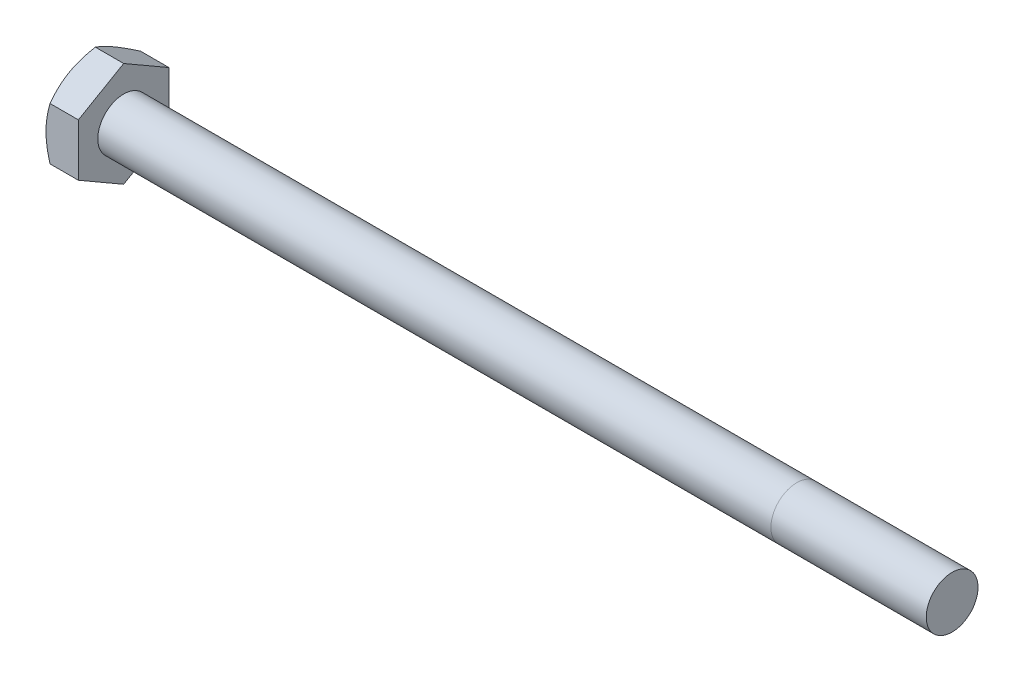
SolidWorks part; units mm, degrees
material "Alloy Steel"
ref_plane "Front Plane" through (0, 0, 0) normal (0, 0, 1) x (1, 0, 0)
ref_plane "Top Plane" through (0, 0, 0) normal (0, 1, 0) x (1, 0, 0)
ref_plane "Right Plane" through (0, 0, 0) normal (1, 0, 0) x (0, 0, -1)
sketch "Sketch1" plane through (0, 0, 0) normal (0, 0, 1) x (1, 0, 0)
  line L0 (-52.7844, 0) -> (52.7844, 0) construction
  line L1 (52.7844, 3.175) -> (52.7844, -3.175) construction
  line L2 (-48.8156, 5.5562) -> (-48.8156, -5.5562) construction
  line L3 (-52.7844, 5.5562) -> (-52.7844, -5.5562) construction
  point P9 (-48.8156, 0)
  point P10 (48.3394, -3.175)
  dimension "D1" = 4.445
  dimension "Screw Dia" = 6.35
  dimension "Hex" = 11.1125
  dimension "Head Ht" = 3.9688
  dimension "Screw Lenght" = 101.6
ref_plane "Plane2" through (52.7844, 0, 0) normal (1, 0, 0) x (0, 0, -1)
sketch "Sketch5" plane through (52.7844, 0, 0) normal (1, 0, 0) x (0, 0, -1)
  circle A0 centre (0, 0) radius 3.175
extrude "Boss-Extrude3" add sketch "Sketch5" against normal up to vertex (101.6 mm away) up to point (-48.8156, 0, 0)
sketch "Sketch9" plane through (52.7844, 0, 0) normal (1, 0, 0) x (0, 0, -1)
  circle A1 centre (0, 0) radius 3.175
  circle A2 centre (0, 0) radius 3.175
  dimension "D1" = 0
curve "Helix/Spiral1" pitch 1.27 height 20.32 turns 16 parameters "Pitch"=1.27
chamfer "Chamfer1" [suppressed] distance 0.9525 angle 45
sketch "Sketch10" plane through (0, 0, 0) normal (0, 0, 1) x (1, 0, 0)
  line L0 (52.7844, 3.175) -> (53.2606, 2.3501)
  line L1 (53.2606, 2.3501) -> (53.4194, 2.3501)
  line L2 (53.4194, 2.3501) -> (53.8956, 3.175)
  line L3 (52.7844, 3.175) -> (53.8956, 3.175)
  line L4 (53.34, 3.175) -> (53.34, 2.3501) construction
  line L5 (53.0225, 2.7626) -> (53.6575, 2.7626) construction
  dimension "D1" = 60
  dimension "D2" = 0.1588
  dimension "D3" = 0.635
sweep "Cut-Sweep1" [suppressed] cut profiles "Sketch10" path "Helix/Spiral1"
sketch "Sketch11" plane through (0, 0, 0) normal (0, 0, 1) x (1, 0, 0)
  line L0 (-48.8156, 3.175) -> (-48.8156, 0)
  line L1 (-48.8156, 0) -> (36.9094, 0)
  line L3 (36.9094, 0) -> (33.7344, 3.175)
  line L4 (-48.8156, 3.175) -> (33.7344, 3.175)
  dimension "D1" = 45
  dimension "MIn Thread" = 19.05
revolve "Revolve1" add sketch "Sketch11" angle 360 about L1
sketch "Sketch6" plane through (-48.8156, 0, 0) normal (-1, 0, 0) x (0, 0, 1)
  line L0 (0, 5.5562) -> (0, -5.5562) construction
  line L1 (5.5563, 3.2079) -> (0, 6.4158)
  line L2 (0, 6.4158) -> (-5.5562, 3.2079)
  line L3 (-5.5562, 3.2079) -> (-5.5562, -3.2079)
  line L4 (-5.5562, -3.2079) -> (0, -6.4158)
  line L5 (0, -6.4158) -> (5.5563, -3.2079)
  line L6 (5.5563, -3.2079) -> (5.5563, 3.2079)
  circle A0 centre (0, 0) radius 5.5563 construction
extrude "Boss-Extrude4" add sketch "Sketch6" along normal up to vertex (3.9688 mm away) up to point (-52.7844, -5.5562, 0)
sketch "Sketch7" plane through (-52.7844, 0, 0) normal (-1, 0, 0) x (0, 0, 1)
  circle A0 centre (0, 0) radius 5.5563 construction
  circle A1 centre (0, 0) radius 5.5563
sketch "Sketch8" plane through (-52.7844, 0, 0) normal (-1, 0, 0) x (0, 0, 1)
  circle A0 centre (0, 0) radius 5.5563 construction
  circle A1 centre (0, 0) radius 5.5563
extrude "Cut-Extrude3" cut sketch "Sketch8" against normal through all draft 60 flip side to cut
sketch "Sketch12" plane through (-52.7844, 0, 0) normal (-1, 0, 0) x (0, 0, 1)
  line L0 (0, 4.2783) -> (0, 2.3892) construction
  line L1 (0.1667, 4.2783) -> (0.1667, 2.3892)
  line L2 (-0.1667, 4.2783) -> (-0.1667, 2.3892)
  line L3 (0, 3.175) -> (0, -3.175) construction
  arc A0 (0.1667, 4.2783) -> (-0.1667, 4.2783) centre (0, 4.2783) ccw
  arc A1 (-0.1667, 2.3892) -> (0.1667, 2.3892) centre (0, 2.3892) ccw
  circle A3 centre (0, 0) radius 2.2225 construction
  circle A4 centre (0, 0) radius 4.445 construction
  point P2 (0, 3.3337)
  dimension "D1" = 4.445
  dimension "D3" = 8.89
  dimension "D2" = 0.3334
extrude "Cut-Extrude4" cut sketch "Sketch12" against normal blind 0.254
pattern_circular "CirPattern1" count 3 over 360 about axis through (-48.8156, 0, 0) along (1, 0, 0) of "Cut-Extrude4"
sketch "Sketch13" plane through (0, 0, 0) normal (0, 1, 0) x (1, 0, 0)
  line L0 (33.7344, -3.175) -> (33.7344, 3.175)
  line L1 (-48.8156, -3.175) -> (52.7844, -3.175) construction
  line L2 (52.7844, 3.175) -> (-48.8156, 3.175) construction
  line L3 (52.7844, -3.175) -> (52.7844, 3.175) construction
  point P8 (33.7344, 0)
  dimension "D1" = 19.05
split line "Split Line4"
equation "\"D2@Sketch10\" = \"Pitch@Helix/Spiral1\"*.125"
equation "\"D3@Sketch10\" = \"Pitch@Helix/Spiral1\"*.5"
equation "\"D3@Helix/Spiral1\" = \"MIn Thread@Sketch11\"+\"Pitch@Helix/Spiral1\""
equation "\"D1@Chamfer1\" = \"Pitch@Helix/Spiral1\"*.75"
equation "\"D1@Sketch12\" = \"Hex@Sketch1\"*.4"
equation "\"D3@Sketch12\" = \"Hex@Sketch1\"*.8"
equation "\"D2@Sketch12\" = \"Hex@Sketch1\"*.03"
equation "\"D1@Sketch1\" = \"Pitch@Helix/Spiral1\"*3.5"
